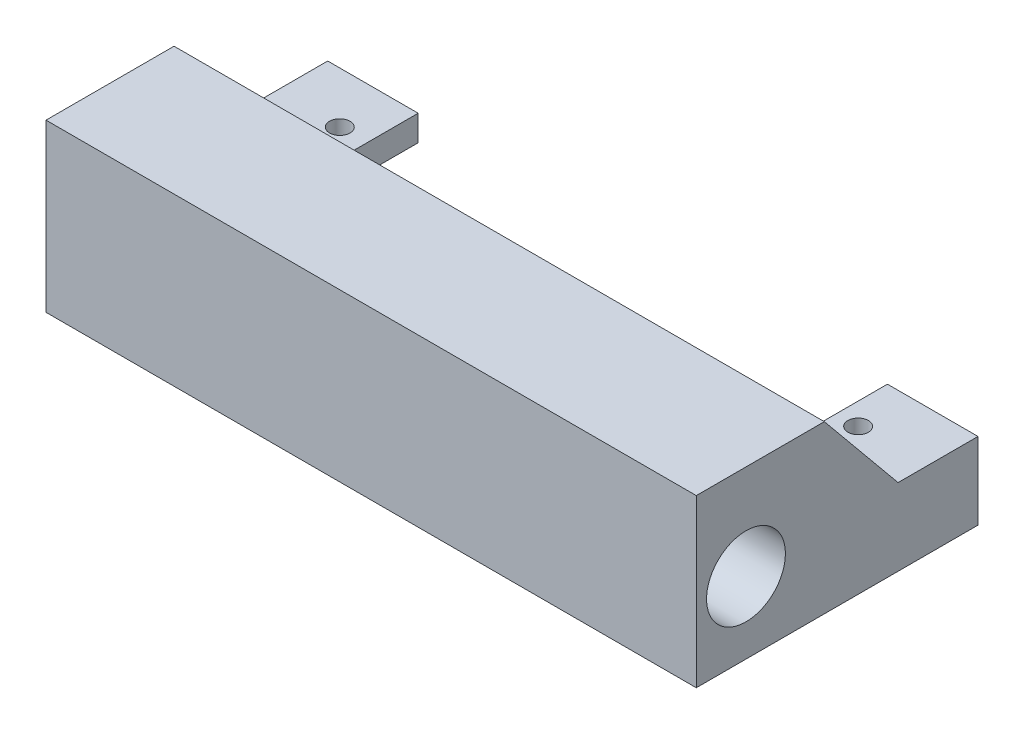
SolidWorks part; units mm, degrees
ref_plane "Front Plane" through (0, 0, 0) normal (0, 0, 1) x (1, 0, 0)
ref_plane "Top Plane" through (0, 0, 0) normal (0, 1, 0) x (1, 0, 0)
ref_plane "Right Plane" through (0, 0, 0) normal (1, 0, 0) x (0, 0, -1)
sketch "Croquis1" plane through (0, 0, 0) normal (0, 1, 0) x (1, 0, 0)
  line L0 (-58.38, 25.2) -> (-45.7, 25.2)
  line L1 (-45.7, 25.2) -> (-45.7, 0)
  line L2 (-45.7, 0) -> (45.7, 0)
  line L3 (45.7, 0) -> (45.7, 25.2)
  line L4 (45.7, 25.2) -> (58.38, 25.2)
  line L5 (58.38, 25.2) -> (58.38, -4.8)
  line L6 (58.38, -4.8) -> (-58.38, -4.8)
  line L7 (-58.38, -4.8) -> (-58.38, 25.2)
  line L8 (-45.7, 0) -> (-45.7, 12.6)
  line L9 (-45.7, 12.6) -> (-58.38, 12.6)
  line L10 (45.7, 12.6) -> (58.38, 12.6)
  dimension "D1" = 45.7
  dimension "D2" = 45.7
  dimension "D3" = 58.38
  dimension "D4" = 58.38
  dimension "D5" = 30
  dimension "D6" = 4.8
  dimension "D7" = 30
  dimension "D8" = 12.68
  dimension "D9" = 12.6
extrude "Saliente-Extruir1" add sketch "Croquis1" along normal blind 5 contours L9 L1 L0 L7 | L10 L3 L2 L1 L9 L7 L6 L5 | L3 L10 L5 L4 region at (-52.04, 0, -18.9) region at (-52.04, 0, -11.4195) region at (52.04, 0, -18.9)
extrude "Saliente-Extruir3" add sketch "Croquis1<4>" against normal blind 5 contours L10 L3 L2 L1 L9 L7 L6 L5 region at (-52.04, 0, -11.4195)
sketch "Croquis1<4>" plane through (0, 0, 0) normal (0, 1, 0) x (1, 0, 0) same geometry as "Croquis1"
extrude "Saliente-Extruir4" add sketch "Croquis1<5>" along normal blind 12.5 contours L10 L3 L2 L1 L9 L7 L6 L5 region at (-52.04, 0, -11.4195)
sketch "Croquis1<5>" plane through (0, 0, 0) normal (0, 1, 0) x (1, 0, 0) same geometry as "Croquis1"
sketch "Croquis2" plane through (45.7, 0, 0) normal (-1, 0, 0) x (0, 0, 1)
  line L0 (-12.6, 0) -> (0, 0)
  line L1 (0, 0) -> (0, -5)
  line L2 (0, -5) -> (-12.6, -5)
  line L3 (-12.6, -5) -> (-12.6, 0)
extrude "Cortar-Extruir1" cut sketch "Croquis2" against normal mid plane 255
sketch "Croquis3" plane through (-58.38, 0, 0) normal (-1, 0, 0) x (0, 0, 1)
  line L0 (0, 0) -> (4.8, 0)
  line L1 (4.8, 12.5) -> (4.8, -5) construction
  line L2 (4.8, 0) -> (4.8, -5)
  line L3 (4.8, -5) -> (0, -5)
  line L4 (0, -5) -> (0, 0)
extrude "Cortar-Extruir2" cut sketch "Croquis3" against normal blind 255
sketch "Croquis4" plane through (0, 0, 4.8) normal (0, 0, 1) x (1, 0, 0)
  line L0 (-58.38, 12.5) -> (-58.38, -10)
  line L1 (-58.38, -10) -> (58.38, -10)
  line L2 (58.38, -10) -> (58.38, 12.5)
  line L3 (58.38, 12.5) -> (-58.38, 12.5)
  line L4 (58.38, 0) -> (-58.38, 0) construction
  line L5 (-58.38, 12.5) -> (-58.38, 22.5)
  line L6 (-58.38, 22.5) -> (58.38, 22.5)
  line L7 (58.38, 22.5) -> (58.38, 12.5)
  line M2 (-58.38, 0) -> (58.38, 0)
  line M3 (58.38, 0) -> (58.38, 12.5)
  line M4 (58.38, 12.5) -> (-58.38, 12.5)
  line M5 (-58.38, 12.5) -> (-58.38, 0)
  dimension "D1" = 10
  dimension "D2" = 10
extrude "Saliente-Extruir5" add sketch "Croquis4" along normal blind 25 contours L1 L2 L0 M2 | M5 M2 M3 M4 | L7 L6 L5 M4 region at (0, 6.25, 4.8) region at (0, 17.5, 4.8) region at (0, -5, 4.8)
sketch "Croquis5" plane through (-58.38, 0, 0) normal (-1, 0, 0) x (0, 0, 1)
  line L1 (4.8, 12.5) -> (-12.6, 12.5) construction
  line L2 (4.8, 0) -> (4.8, -10) construction
  circle A0 centre (20.1, 4) radius 4.5
  dimension "D1" = 9
  dimension "D2" = 15.3
  dimension "D3" = 8.5
extrude "Cortar-Extruir3" cut sketch "Croquis5" against normal blind 155
sketch "Croquis6" plane through (-58.38, 0, 0) normal (-1, 0, 0) x (0, 0, 1)
  circle A0 centre (20.1, 4) radius 7.7
  dimension "D1" = 15.4
extrude "Cortar-Extruir4" cut sketch "Croquis6" against normal blind 20.3
mirror "Simetría1" about plane through (0, 0, 0) normal (1, 0, 0) of "Cortar-Extruir4"
sketch "Croquis7" plane through (-58.38, 0, 0) normal (-1, 0, 0) x (0, 0, 1)
  line L0 (-25.2, 5) -> (-25.2, -10)
  line L1 (-25.2, -10) -> (29.8, -10)
  line L2 (29.8, -10) -> (29.8, 22.5)
  line L3 (29.8, 22.5) -> (4.8, 22.5)
  line L4 (4.8, 22.5) -> (4.8, 12.5)
  line L5 (4.8, 12.5) -> (-12.6, 12.5)
  line L6 (-12.6, 12.5) -> (-12.6, 5)
  line L7 (-12.6, 5) -> (-25.2, 5)
  circle A0 centre (20.1, 4) radius 7.7
extrude "Saliente-Extruir6" add sketch "Croquis7" along normal blind 5
mirror "Simetría2" about plane through (0, 0, 0) normal (1, 0, 0) of "Saliente-Extruir6"
sketch "Croquis8" plane through (0, 0, -25.2) normal (0, 0, -1) x (-1, 0, 0)
  line L0 (-58.38, -10) -> (-59.38, -10)
  line L1 (-63.38, -10) -> (-58.38, -10) construction
  line L2 (-59.38, -10) -> (-59.38, 0)
  line L3 (-59.38, 0) -> (-58.38, 0)
  line L4 (-58.38, 0) -> (-46.7, 0)
  line L5 (-45.7, 0) -> (-58.38, 0) construction
  line L6 (-46.7, 0) -> (-46.7, 5)
  line L7 (-45.7, 5) -> (-63.38, 5) construction
  line L8 (-46.7, 5) -> (-46.7, 12.5)
  line L9 (-46.7, 12.5) -> (-42.1848, 12.5)
  line L10 (-42.1848, 12.5) -> (-42.1848, -10)
  line L11 (-42.1848, -10) -> (-58.38, -10)
  line L12 (-45.7, 5) -> (-45.7, 0) construction
  dimension "D1" = 1
  dimension "D2" = 1
  dimension "D3" = 7.5
extrude "Cortar-Extruir5" cut sketch "Croquis8" against normal blind 25.2
sketch "Croquis9" plane through (0, 0, 0) normal (0, 0, -1) x (-1, 0, 0)
  line L0 (-59.38, -10) -> (-58.38, -10)
  line L1 (-58.38, -10) -> (-58.38, 0)
  line L2 (-58.38, 0) -> (-59.38, 0)
  line L3 (-59.38, 0) -> (-59.38, -10)
extrude "Cortar-Extruir6" cut sketch "Croquis9" against normal blind 4.8
sketch "Croquis10" plane through (0, -10, 0) normal (0, -1, 0) x (1, 0, 0)
  line L0 (59.38, 4.8) -> (59.38, 5.2)
  line L1 (59.38, 5.2) -> (-58.38, 5.2)
  line L2 (-58.38, 5.2) -> (-58.38, 4.8)
  line L3 (-58.38, 4.8) -> (59.38, 4.8)
  dimension "D1" = 0.4
extrude "Cortar-Extruir7" cut sketch "Croquis10" against normal blind 10
sketch "Croquis11" plane through (0, 5, 0) normal (0, 1, 0) x (1, 0, 0)
  line L0 (63.38, 25.2) -> (59.38, 25.2) construction
  line L1 (46.7, 25.2) -> (63.38, 25.2) construction
  line L2 (59.38, 25.2) -> (50.98, 25.2) construction
  line L3 (50.98, 25.2) -> (50.98, 12.6) construction
  line L4 (63.38, 12.6) -> (46.7, 12.6) construction
  circle A0 centre (50.98, 15.2) radius 2
  dimension "D3" = 4
  dimension "D1" = 4
  dimension "D2" = 8.4
  dimension "D4" = 10
extrude "Cortar-Extruir8" cut sketch "Croquis11" against normal blind 10
sketch "Croquis12" plane through (63.38, 0, 0) normal (1, 0, 0) x (0, 0, -1)
  line L0 (12.6, 5) -> (9.6, 5)
  line L1 (9.6, 5) -> (9.6, 12.5)
  line L2 (-4.8, 12.5) -> (12.6, 12.5) construction
  line L3 (9.6, 12.5) -> (12.6, 12.5)
  line L4 (12.6, 12.5) -> (12.6, 5)
  dimension "D1" = 3
extrude "Cortar-Extruir9" cut sketch "Croquis12" against normal blind 220
sketch "Croquis13" plane through (63.38, 0, 0) normal (1, 0, 0) x (0, 0, -1)
  line L3 (9.6, 12.5) -> (9.6, 5)
  line L4 (-4.8, 22.5) -> (9.6, 5)
  line L5 (-4.8, 22.5) -> (9.6, 22.5)
  line L6 (9.6, 22.5) -> (9.6, 12.5)
extrude "Cortar-Extruir10" cut sketch "Croquis13" against normal blind 220
sketch "Croquis14" plane through (63.38, 0, 0) normal (1, 0, 0) x (0, 0, -1)
  line L0 (-4.8, 22.5) -> (3.4286, 12.5)
  line L1 (3.4286, 12.5) -> (-4.8, 12.5)
  line L2 (-4.8, 12.5) -> (-4.8, 22.5)
extrude "Saliente-Extruir7" add sketch "Croquis14" against normal blind 16.68
mirror "Simetría4" about plane through (0, 0, 0) normal (1, 0, 0) of "Saliente-Extruir7"
sketch "Croquis15" plane through (63.38, 0, 0) normal (1, 0, 0) x (0, 0, -1)
  line L0 (-29.8, 22.5) -> (-4.8, 22.5)
  line L1 (-4.8, 22.5) -> (9.6, 5)
  line L2 (9.6, 5) -> (25.2, 5)
  line L3 (25.2, 5) -> (25.2, -10)
  line L4 (25.2, -10) -> (-29.8, -10)
  line L5 (-29.8, -10) -> (-29.8, 22.5)
  circle A0 centre (-20.1, 4) radius 7.7
extrude "Saliente-Extruir8" add sketch "Croquis15" along normal blind 1
sketch "Croquis16" plane through (38.08, 0, 0) normal (1, 0, 0) x (0, 0, -1)
  circle A0 centre (-20.1, 4) radius 7.7
  circle A1 centre (-20.1, 4) radius 4.5
  dimension "D1" = 9
  dimension "D2" = 15.4
extrude "Saliente-Extruir9" add sketch "Croquis16" along normal blind 1.8
sketch "Croquis17" plane through (-46.7, 0, 0) normal (1, 0, 0) x (0, 0, -1)
  line L0 (-4.8, 12.5) -> (3.4286, 12.5)
  line L1 (3.4286, 12.5) -> (-4.8, 22.5)
  line L2 (-4.8, 22.5) -> (-4.8, 12.5)
extrude "Saliente-Extruir10" add sketch "Croquis17" along normal blind 1
sketch "Croquis18" plane through (0, 0, -25.2) normal (0, 0, -1) x (-1, 0, 0)
  line L0 (58.38, -10) -> (58.38, 0)
  line L1 (58.38, 0) -> (45.7, 0)
  line L2 (45.7, 0) -> (45.7, 5)
  line L3 (45.7, 5) -> (44.92, 5)
  line L4 (44.92, 5) -> (44.92, 0)
  line L5 (44.92, 0) -> (58.28, 0)
  line L6 (58.28, 0) -> (58.28, -10)
  line L7 (58.28, -10) -> (58.38, -10)
  line M10 (45.7, 5) -> (45.7, 0)
  dimension "D1" = 0.1
  dimension "D2" = 0
  dimension "D3" = 0.78
extrude "Saliente-Extruir11" add sketch "Croquis18" against normal blind 31 contours L4 L5 L3 M10 region at (-45.31, 2.5, -25.2)
sketch "Croquis19" plane through (-45.7, 0, 0) normal (1, 0, 0) x (0, 0, -1)
  line L0 (0, 5) -> (9.6, 5)
  line L1 (9.6, 5) -> (-4.8, 22.5)
  line L2 (-4.8, 22.5) -> (-4.8, 12.5)
  line L3 (-4.8, 12.5) -> (0, 12.5)
  line L4 (0, 12.5) -> (0, 5)
extrude "Saliente-Extruir12" add sketch "Croquis19" along normal blind 0.78
sketch "Croquis20" plane through (0, 0, -25.2) normal (0, 0, -1) x (-1, 0, 0)
  line L0 (63.38, -10) -> (62.58, -10)
  line L1 (63.38, -10) -> (58.38, -10) construction
  line L2 (62.58, -10) -> (62.58, 24.7831)
  line L3 (62.58, 24.7831) -> (64.5744, 24.7831)
  line L4 (64.5744, 24.7831) -> (64.5744, -10)
  line L5 (64.5744, -10) -> (63.38, -10)
  dimension "D1" = 0.8
extrude "Cortar-Extruir11" cut sketch "Croquis20" against normal blind 220.78
sketch "Croquis21" plane through (0, 5, 0) normal (0, 1, 0) x (1, 0, 0)
  line L0 (-44.92, 9.6) -> (-44.92, 25.2) construction
  line L1 (-62.58, 25.2) -> (-44.92, 25.2) construction
  circle A0 centre (-50.22, 15.2) radius 2
  dimension "D1" = 4
  dimension "D2" = 5.3
  dimension "D3" = 10
extrude "Cortar-Extruir12" cut sketch "Croquis21" against normal blind 220.78
sketch "Croquis22" plane through (0, 0, -25.2) normal (0, 0, -1) x (-1, 0, 0)
  line L0 (-59.38, -10) -> (-59.18, -10)
  line L1 (-59.18, -10) -> (-59.18, 0)
  line L2 (-46.7, 0) -> (-59.38, 0) construction
  line L3 (-59.18, 0) -> (-59.38, 0)
  line L4 (-59.38, 0) -> (-59.38, -10)
  dimension "D1" = 0.2
extrude "Saliente-Extruir13" add sketch "Croquis22" against normal blind 30.78
